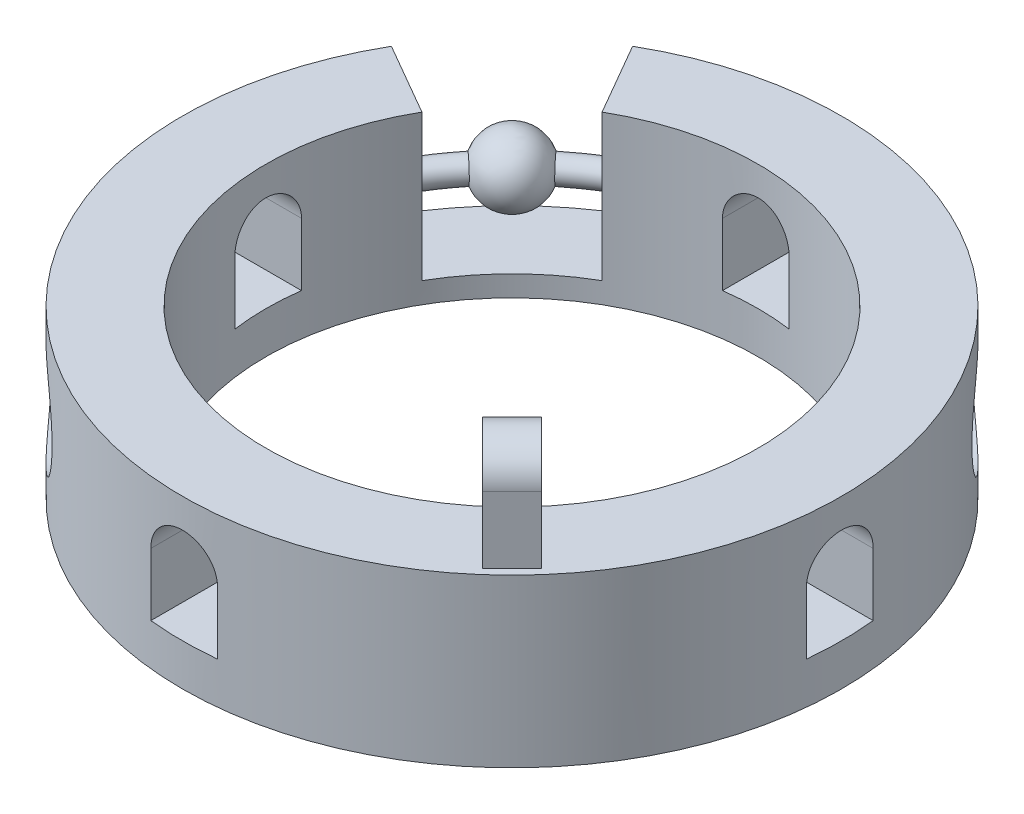
SolidWorks part; units mm, degrees
ref_plane "Front Plane" through (0, 0, 0) normal (0, 0, 1) x (1, 0, 0)
ref_plane "Top Plane" through (0, 0, 0) normal (0, 1, 0) x (1, 0, 0)
ref_plane "Right Plane" through (0, 0, 0) normal (1, 0, 0) x (0, 0, -1)
sketch "Sketch1" plane through (0, 0, 0) normal (0, 1, 0) x (1, 0, 0)
  circle A0 centre (0, 0) radius 29.5
  circle A1 centre (0, 0) radius 39.5
  dimension "D1" = 59
  dimension "D2" = 79
extrude "Boss-Extrude1" add sketch "Sketch1" along normal blind 20
ref_plane "Plane1" through (0, 0, 0) normal (0.7071, 0, -0.7071) x (-0.7071, 0, -0.7071)
sketch "Sketch2" plane through (0, 0, 0) normal (1, 0, 0) x (0, 0, -1)
  line L0 (0, 0) -> (0, 30.0667) construction
  line L1 (4, 5) -> (-4, 5)
  line L2 (-4, 5) -> (-4, 12.5)
  line L3 (4, 5) -> (4, 12.5)
  arc A0 (-4, 12.5) -> (4, 12.5) centre (0, 12.5) cw
  dimension "D6" = 4
  dimension "D1" = 8
  dimension "D2" = 4
  dimension "D3" = 5
  dimension "D4" = 7.5
  dimension "D5" = 7.5
extrude "Cut-Extrude1" cut sketch "Sketch2" against normal through all
extrude "Cut-Extrude2" cut sketch "Sketch2<2>" along normal through all
sketch "Sketch2<2>" plane through (0, 0, 0) normal (1, 0, 0) x (0, 0, -1) same geometry as "Sketch2"
mirror "Mirror1" about plane through (0, 0, 0) normal (0.7071, 0, -0.7071) of "Cut-Extrude2", "Cut-Extrude1"
sketch "Sketch4" plane through (0, 0, 0) normal (0.7071, 0, -0.7071) x (-0.7071, 0, -0.7071)
  line L0 (0, 0) -> (0, 44.1067) construction
  circle A0 centre (0, 10) radius 3.175
  dimension "D1" = 6.35
  dimension "D2" = 10
extrude "Cut-Extrude3" cut sketch "Sketch4" against normal up to next
extrude "Cut-Extrude4" cut sketch "Sketch4<2>" along normal up to next
sketch "Sketch4<2>" plane through (0, 0, 0) normal (0.7071, 0, -0.7071) x (-0.7071, 0, -0.7071) same geometry as "Sketch4"
ref_plane "Plane2" through (0, 0, 0) normal (0.7071, 0, 0.7071) x (0.7071, 0, -0.7071)
sketch "Sketch5" plane through (0, 20, 0) normal (0, 1, 0) x (1, 0, 0)
  line L0 (13.6827, -13.6827) -> (-13.6827, 13.6827) construction
  line L1 (-27.9307, 27.9307) -> (27.9307, -27.9307) construction
  line L2 (25.4558, -28.9914) -> (28.9914, -25.4558)
  line L3 (25.4558, -28.9914) -> (19.799, -23.3345)
  line L4 (28.9914, -25.4558) -> (23.3345, -19.799)
  line L5 (19.799, -23.3345) -> (23.3345, -19.799)
  line L6 (25.4558, -28.9914) -> (23.3345, -19.799) construction
  line L7 (28.9914, -25.4558) -> (19.799, -23.3345) construction
  circle A0 centre (0, 0) radius 39.5 construction
  circle A1 centre (0, 0) radius 29.5 construction
  point P7 (24.3952, -24.3952)
  dimension "D1" = 34.5
  dimension "D2" = 8
  dimension "D3" = 5
extrude "Boss-Extrude2" add sketch "Sketch5" along normal blind 13
sketch "Sketch6" plane through (1.7678, 0, -1.7678) normal (0.7071, 0, -0.7071) x (-0.7071, 0, -0.7071)
  line L0 (-38.5, 33) -> (-38.5, 20) construction
  line L1 (-38.5, 33) -> (-30.5, 33) construction
  line L2 (-30.5, 33) -> (-30.5, 20) construction
  line L4 (-38.5, 28) -> (-38.5, 33)
  line L8 (-38.5, 33) -> (-30.5, 33)
  line L9 (-30.5, 33) -> (-30.5, 28)
  arc A0 (-38.5, 28) -> (-30.5, 28) centre (-34.5, 28) cw
  dimension "D3" = 4
  dimension "D1" = 4
  dimension "D2" = 5
extrude "Cut-Extrude7" cut sketch "Sketch6" against normal up to next
sketch "Sketch7" plane through (1.7678, 0, -1.7678) normal (0.7071, 0, -0.7071) x (-0.7071, 0, -0.7071)
  circle A0 centre (-34.5, 28) radius 1
  dimension "D1" = 2
extrude "Cut-Extrude8" cut sketch "Sketch7" against normal up to next
ref_plane "Plane3" through (27.9307, 0, -27.9307) normal (0.7071, 0, -0.7071) x (-0.7071, 0, -0.7071)
sketch "Sketch8" plane through (27.9307, 0, -27.9307) normal (0.7071, 0, -0.7071) x (-0.7071, 0, -0.7071)
  circle A0 centre (0, 10) radius 6.35
  dimension "D1" = 12.7
extrude "Cut-Extrude9" cut sketch "Sketch8" against normal blind 1
mirror "Mirror3" about plane through (0, 0, 0) normal (0.7071, 0, -0.7071) of "Cut-Extrude9"
ref_plane "Plane4" through (0, 0, 0) normal (0.7071, 0, -0.7071) x (-0.7071, 0, -0.7071)
ref_plane "Plane5" through (0, 10, 0) normal (0, 1, 0) x (1, 0, 0)
ref_axis "Ball Join Axis" through (-41.2502, 10, -41.2502) along (0.7071, 0, 0.7071)
sketch "Sketch9" plane through (0, 20, 0) normal (0, 1, 0) x (1, 0, 0)
  line L0 (-14.75, 25.5477) -> (-19.75, 34.208)
  line L1 (-25.5477, 14.75) -> (-34.208, 19.75)
  line L2 (-41.2502, 41.2502) -> (45.8258, -45.8258) construction
  arc A0 (-14.75, 25.5477) -> (-25.5477, 14.75) centre (0, 0) ccw
  arc A1 (-19.75, 34.208) -> (-34.208, 19.75) centre (0, 0) ccw
  dimension "D1" = 15
  dimension "D2" = 15
extrude "Cut-Extrude11" cut sketch "Sketch9" against normal blind 17.5 contours L1 A1 L0 A0
sketch "Sketch10" plane through (0, 0, 0) normal (0.7071, 0, -0.7071) x (-0.7071, 0, -0.7071)
  line L0 (58.3366, 10) -> (-64.8075, 10) construction
  line L1 (30.5, 10) -> (38.5, 10)
  arc A0 (38.5, 10) -> (30.5, 10) centre (34.5, 10) ccw
  dimension "D3" = 4
  dimension "D1" = 0
  dimension "D2" = 34.5
revolve "Revolve2" add sketch "Sketch10" angle 360 about axis through (-41.2502, 10, -41.2502) along (0.7071, 0, 0.7071)
sketch "Sketch12" plane through (0, 10, 0) normal (0, 1, 0) x (1, 0, 0)
  arc A0 (-14.5794, 31.2681) -> (-31.1144, 14.9045) centre (0, 0) ccw
  dimension "D1" = 69
sketch "Sketch14" plane through (0, 0, 0) normal (0.7071, 0, -0.7071) x (-0.7071, 0, -0.7071)
  line L0 (58.3366, 10) -> (-64.8075, 10) construction
  circle A0 centre (34.5, 10) radius 1.5
  dimension "D1" = 3
  dimension "D2" = 0
  dimension "D3" = 34.5
sweep "Sweep1" add profiles "Sketch14" path "Sketch12"
